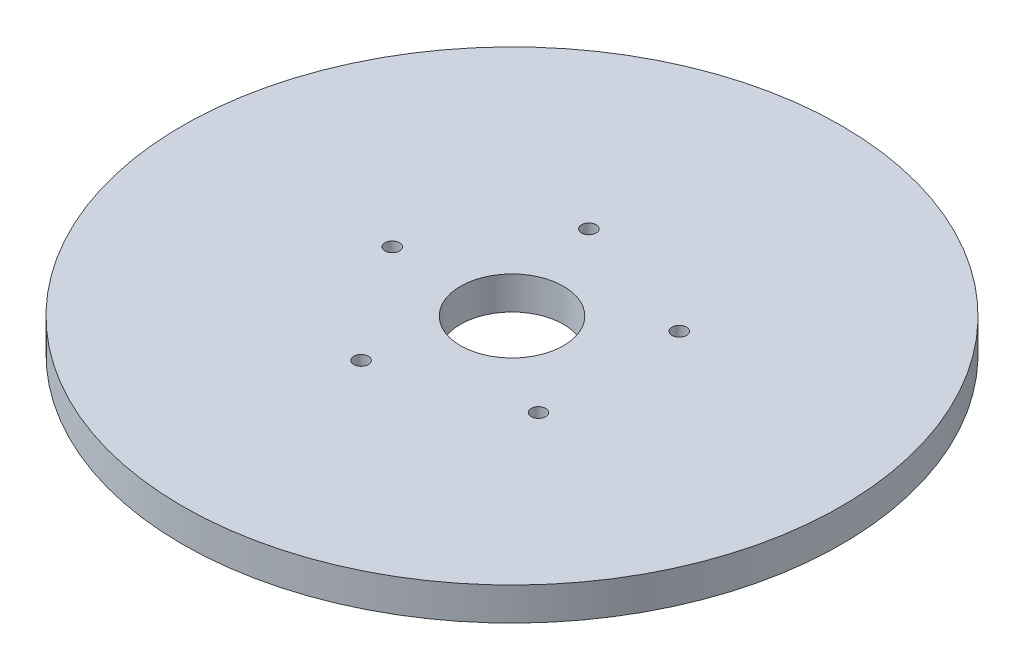
SolidWorks part; units mm, degrees
ref_plane "Front Plane" through (0, 0, 0) normal (0, 0, 1) x (1, 0, 0)
ref_plane "Top Plane" through (0, 0, 0) normal (0, 1, 0) x (1, 0, 0)
ref_plane "Right Plane" through (0, 0, 0) normal (1, 0, 0) x (0, 0, -1)
sketch "Sketch1" plane through (0, 0, 0) normal (0, 1, 0) x (1, 0, 0)
  circle A0 centre (0, 0) radius 80
  dimension "FLANGE_OD" = 160
extrude "Boss-Extrude1" add sketch "Sketch1" along normal blind 8
sketch "Sketch2" plane through (0, 0, 0) normal (0, 1, 0) x (1, 0, 0)
  circle A0 centre (0, 0) radius 12.5
  dimension "BORE_D" = 25
extrude "Cut-Extrude1" cut sketch "Sketch2" along normal through all
sketch "Sketch3" plane through (0, 8, 0) normal (0, 1, 0) x (1, 0, 0)
  circle A0 centre (0, 0) radius 29.0705 construction
  circle A1 centre (-29.0705, 0) radius 1.7609
  dimension "BOLT_D" = 3.5218
  dimension "BOLT_PCD" = 58.1411
extrude "Cut-Extrude2" cut sketch "Sketch3" against normal blind 6.6798
pattern_circular "CirPattern1" count 5 over 360 about axis through (0, 0, 0) along (0, 1, 0) of "Cut-Extrude2"
